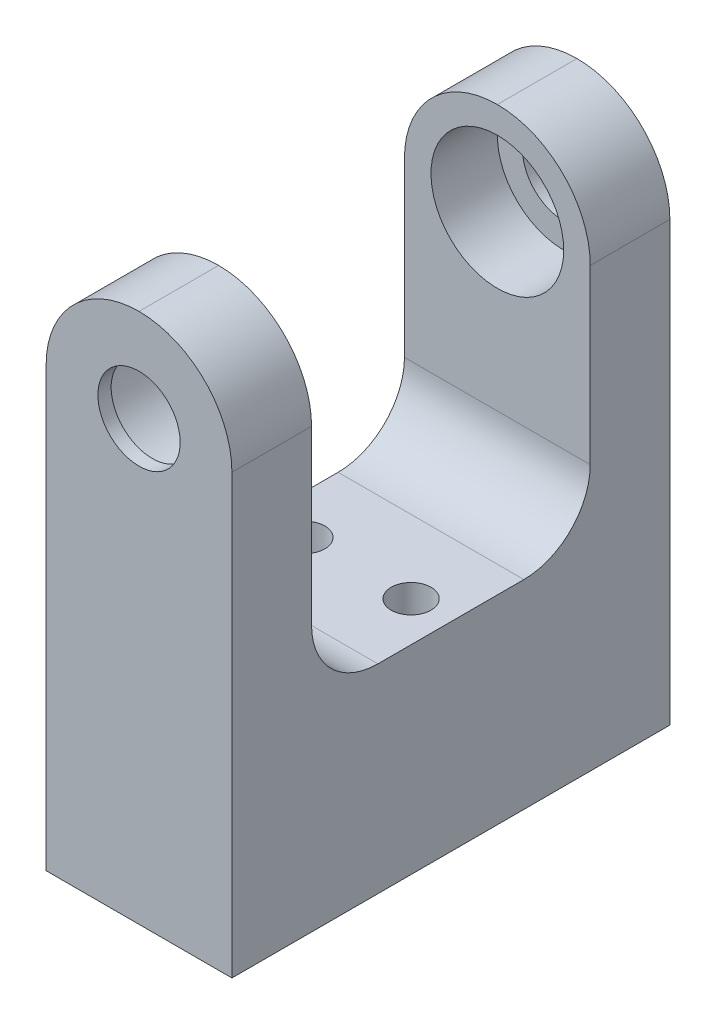
SolidWorks part; units mm, degrees
material "AISI 4130 钢，退火温度为 865C"
ref_plane "前视基准面" through (0, 0, 0) normal (0, 0, 1) x (1, 0, 0)
ref_plane "上视基准面" through (0, 0, 0) normal (0, 1, 0) x (1, 0, 0)
ref_plane "右视基准面" through (0, 0, 0) normal (1, 0, 0) x (0, 0, -1)
sketch "草图4" plane through (0, 0, 0) normal (1, 0, 0) x (0, 0, -1)
  line L0 (0, 0) -> (16.5, 0)
  line L1 (16.5, 0) -> (16.5, 40)
  line L2 (16.5, 40) -> (10.5, 40)
  line L3 (10.5, 40) -> (10.5, 20)
  line L4 (5.5, 15) -> (-5.5, 15)
  line L5 (-10.5, 20) -> (-10.5, 40)
  line L6 (-10.5, 40) -> (-16.5, 40)
  line L7 (-16.5, 40) -> (-16.5, 0)
  line L8 (-16.5, 0) -> (0, 0)
  arc A2 (10.5, 20) -> (5.5, 15) centre (5.5, 20) cw
  arc A3 (-5.5, 15) -> (-10.5, 20) centre (-5.5, 20) cw
  dimension "D5" = 5
  dimension "D1" = 40
  dimension "D2" = 16.5
  dimension "D3" = 6
  dimension "D4" = 15
extrude "凸台-拉伸1" add sketch "草图4" along normal blind 14
fillet "圆角1" radius 7 4 edges at (0, 40, 13.5) (0, 40, -13.5) (14, 40, -13.5) (14, 40, 13.5)
sketch "草图7" plane through (0, 0, 16.5) normal (0, 0, 1) x (1, 0, 0)
  circle A0 centre (7, 33) radius 5
extrude "切除-拉伸1" cut sketch "草图7" against normal blind 31 from offset 1 offset against normal yes
sketch "草图8" plane through (0, 0, 16.5) normal (0, 0, 1) x (1, 0, 0)
  circle A0 centre (7, 33) radius 3.1
extrude "切除-拉伸2" cut sketch "草图8" against normal blind 35 contours A0
sketch "草图10" plane through (0, 15, 0) normal (0, 1, 0) x (1, 0, 0)
  line L0 (0, 5.5) -> (0, -5.5) construction
  line L1 (14, 5.5) -> (14, -5.5) construction
  circle A0 centre (3, 0) radius 1.5
  circle A1 centre (11, 0) radius 1.5
  dimension "D1" = 3
  dimension "D2" = 3
extrude "切除-拉伸3" cut sketch "草图10" against normal blind 20 from offset 2
